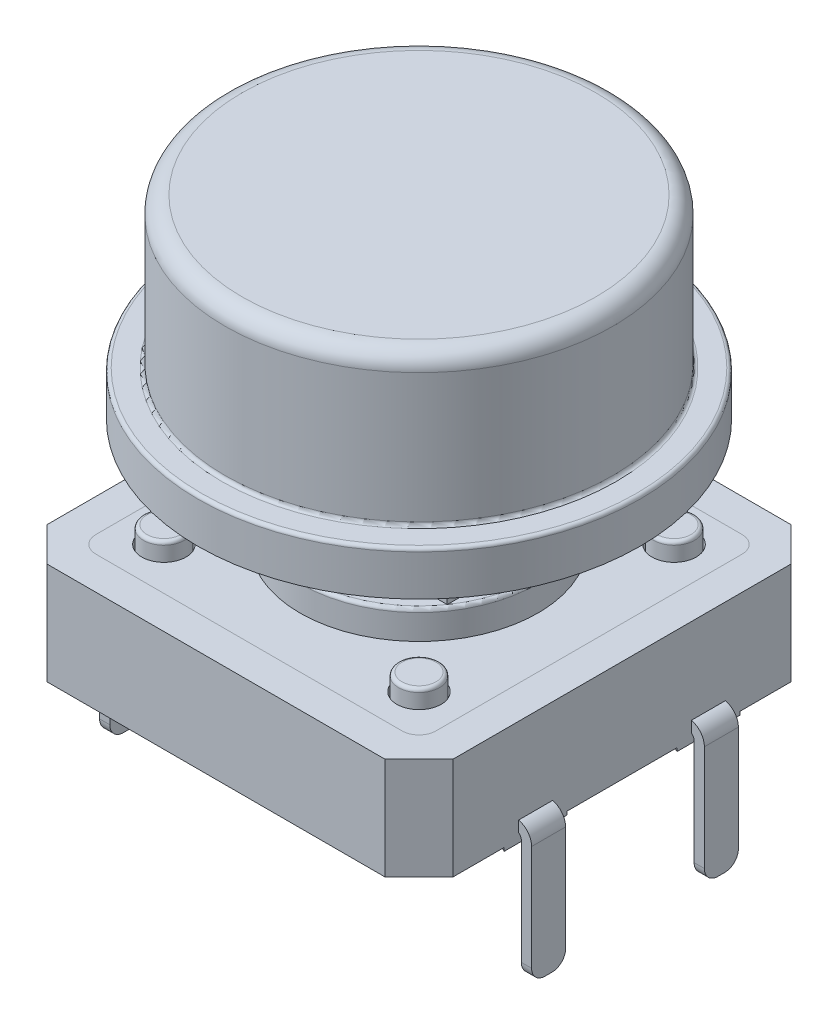
SolidWorks part; units mm, degrees
other "Metal Cover"
other "Button Body"
other "Plastic Button"
other "Connection 1"
other "Connection 2"
ref_plane "Front Plane" through (0, 0, 0) normal (0, 0, 1) x (1, 0, 0)
ref_plane "Top Plane" through (0, 0, 0) normal (0, 1, 0) x (1, 0, 0)
ref_plane "Right Plane" through (0, 0, 0) normal (1, 0, 0) x (0, 0, -1)
sketch "Sketch1" plane through (0, 0, 0) normal (0, 1, 0) x (1, 0, 0)
  line L0 (-5.97, 0) -> (5.97, 0) construction
  line L1 (-5.97, 5.97) -> (5.97, 5.97)
  line L2 (-5.97, 5.97) -> (-5.97, -5.97)
  line L3 (-5.97, -5.97) -> (5.97, -5.97)
  line L4 (5.97, 5.97) -> (5.97, -5.97)
  line L6 (-6.35, 2.54) -> (6.35, 2.54) construction
  line L7 (-6.35, 2.54) -> (-6.35, -2.54) construction
  line L8 (-6.35, -2.54) -> (6.35, -2.54) construction
  line L9 (6.35, 2.54) -> (6.35, -2.54) construction
  line L10 (-6.35, 2.54) -> (6.35, -2.54) construction
  line L11 (-6.35, -2.54) -> (6.35, 2.54) construction
  circle A0 centre (-6.35, 2.54) radius 1 construction
  circle A1 centre (6.35, 2.54) radius 1 construction
  circle A2 centre (6.35, -2.54) radius 1 construction
  circle A3 centre (-6.35, -2.54) radius 1 construction
  point P6 (0, 0)
  dimension "D5" = 2
  dimension "D1" = 11.94
  dimension "D2" = 11.94
  dimension "D3" = 12.7
  dimension "D4" = 5.08
extrude "Boss-Extrude1" add sketch "Sketch1" against normal blind 3
sketch "Sketch2" plane through (0, 0, 0) normal (0, 1, 0) x (1, 0, 0)
  line L1 (-5, 5) -> (5, 5)
  line L2 (-5, 5) -> (-5, -5)
  line L3 (-5, -5) -> (5, -5)
  line L4 (5, 5) -> (5, -5)
  line L5 (-5, 5) -> (5, -5) construction
  line L6 (-5, -5) -> (5, 5) construction
  point P0 (0, 0)
  dimension "D1" = 10
extrude "Cut-Extrude1" cut sketch "Sketch2" against normal blind 0.5
fillet "Fillet1" radius 0.5 4 edges at (-5, -0.25, 5) (5, -0.25, 5) (5, -0.25, -5) (-5, -0.25, -5)
chamfer "Chamfer1" distance 1 angle 45 4 edges at (5.97, -1.5, -5.97) (-5.97, -1.5, -5.97) (-5.97, -1.5, 5.97) (5.97, -1.5, 5.97)
sketch "Sketch3" plane through (0, -0.5, 0) normal (0, 1, 0) x (1, 0, 0)
  line L4 (-5, 4.5) -> (-5, -4.5)
  line L5 (-4.5, -5) -> (4.5, -5)
  line L6 (5, -4.5) -> (5, 4.5)
  line L7 (4.5, 5) -> (-4.5, 5)
  line L8 (-5, 4.5) -> (-5, -4.5)
  line L9 (-4.5, -5) -> (4.5, -5)
  line L10 (5, -4.5) -> (5, 4.5)
  line L11 (4.5, 5) -> (-4.5, 5)
  arc A4 (-5, -4.5) -> (-4.5, -5) centre (-4.5, -4.5) ccw
  arc A5 (4.5, -5) -> (5, -4.5) centre (4.5, -4.5) ccw
  arc A6 (5, 4.5) -> (4.5, 5) centre (4.5, 4.5) ccw
  arc A7 (-4.5, 5) -> (-5, 4.5) centre (-4.5, 4.5) ccw
  arc A8 (-5, -4.5) -> (-4.5, -5) centre (-4.5, -4.5) ccw
  arc A9 (4.5, -5) -> (5, -4.5) centre (4.5, -4.5) ccw
  arc A10 (5, 4.5) -> (4.5, 5) centre (4.5, 4.5) ccw
  arc A11 (-4.5, 5) -> (-5, 4.5) centre (-4.5, 4.5) ccw
  dimension "D1" = 0
extrude "Boss-Extrude2" add sketch "Sketch3" along normal blind 0.5 separate body
sketch "Sketch4" plane through (0, 0, 0) normal (0, 1, 0) x (1, 0, 0)
  line L1 (-3.75, 3.75) -> (3.75, 3.75) construction
  line L2 (-3.75, 3.75) -> (-3.75, -3.75) construction
  line L3 (-3.75, -3.75) -> (3.75, -3.75) construction
  line L4 (3.75, 3.75) -> (3.75, -3.75) construction
  line L5 (-3.75, 3.75) -> (3.75, -3.75) construction
  line L6 (-3.75, -3.75) -> (3.75, 3.75) construction
  circle A0 centre (0, 0) radius 3.5
  circle A1 centre (-3.75, 3.75) radius 0.65
  circle A2 centre (3.75, 3.75) radius 0.65
  circle A3 centre (3.75, -3.75) radius 0.65
  circle A4 centre (-3.75, -3.75) radius 0.65
  dimension "D1" = 7.5
  dimension "D2" = 7
  dimension "D3" = 1.3
extrude "Cut-Extrude2" cut sketch "Sketch4" against normal up to surface (0.5 mm away) up to face at (0, -0.5, 0)
sketch "Sketch5" plane through (0, -0.5, 0) normal (0, 1, 0) x (1, 0, 0)
  circle A0 centre (0, 0) radius 3.45 construction
  circle A1 centre (-3.75, 3.75) radius 0.6
  circle A2 centre (3.75, 3.75) radius 0.6
  circle A3 centre (3.75, -3.75) radius 0.6
  circle A4 centre (-3.75, -3.75) radius 0.6
  dimension "D1" = 6.9
  dimension "D2" = 1.2
extrude "Boss-Extrude3" add sketch "Sketch5" along normal blind 1
sketch "Sketch6" plane through (0, -0.5, 0) normal (0, 1, 0) x (1, 0, 0)
  circle A0 centre (0, 0) radius 3.45 construction
  circle A1 centre (0, 0) radius 3.45
extrude "Boss-Extrude4" add sketch "Sketch6" along normal blind 1.3
sketch "Sketch7" plane through (0, 0.8, 0) normal (0, 1, 0) x (1, 0, 0)
  line L1 (-1.35, 1.35) -> (1.35, 1.35)
  line L2 (-1.35, 1.35) -> (-1.35, -1.35)
  line L3 (-1.35, -1.35) -> (1.35, -1.35)
  line L4 (1.35, 1.35) -> (1.35, -1.35)
  line L5 (-1.35, 1.35) -> (1.35, -1.35) construction
  line L6 (-1.35, -1.35) -> (1.35, 1.35) construction
  point P0 (0, 0)
  dimension "D1" = 2.7
extrude "Boss-Extrude5" add sketch "Sketch7" along normal blind 1.3
sketch "Sketch8" plane through (0, 2.1, 0) normal (0, 1, 0) x (1, 0, 0)
  line L0 (0, 1.925) -> (0, -1.925) construction
  line L1 (-1.725, 1.925) -> (1.725, 1.925)
  line L2 (-1.925, 1.725) -> (-1.925, -1.725)
  line L3 (-1.725, -1.925) -> (1.725, -1.925)
  line L4 (1.925, 1.725) -> (1.925, -1.725)
  arc A0 (-1.725, 1.925) -> (-1.925, 1.725) centre (-1.725, 1.725) ccw
  arc A1 (-1.925, -1.725) -> (-1.725, -1.925) centre (-1.725, -1.725) ccw
  arc A2 (1.725, -1.925) -> (1.925, -1.725) centre (1.725, -1.725) ccw
  arc A3 (1.725, 1.925) -> (1.925, 1.725) centre (1.725, 1.725) cw
  dimension "D3" = 0.2
  dimension "D1" = 3.85
  dimension "D2" = 3.85
extrude "Boss-Extrude6" add sketch "Sketch8" along normal blind 2.1
sketch "Sketch9" plane through (0, 4.2, 0) normal (0, 1, 0) x (1, 0, 0)
  circle A0 centre (0, 0) radius 1
  dimension "D1" = 2
extrude "Cut-Extrude3" cut sketch "Sketch9" against normal blind 1.5
sketch "Sketch10" plane through (0, 0, 0) normal (1, 0, 0) x (0, 0, -1)
  line L0 (0, 0) -> (0, -3) construction
  line L1 (-4.97, -3) -> (4.97, -3) construction
  line L2 (0, 0) -> (0, 3.2) construction
  line L3 (0, 3.2) -> (-6.5, 3.2)
  line L4 (-6.5, 3.2) -> (-6.5, 4.4)
  line L5 (-6.4, 4.5) -> (-5.7, 4.5)
  line L6 (-5.7, 4.5) -> (-5.7, 8.4)
  line L7 (-5.2, 8.9) -> (0, 8.9)
  line L8 (0, 8.9) -> (0, 3.2)
  arc A0 (-5.7, 8.4) -> (-5.2, 8.9) centre (-5.2, 8.4) cw
  arc A1 (-6.5, 4.4) -> (-6.4, 4.5) centre (-6.4, 4.4) cw
  dimension "D1" = 6.5
  dimension "D6" = 0.5
  dimension "D7" = 0.1
  dimension "D2" = 5.7
  dimension "D3" = 1.3
  dimension "D4" = 3.2
  dimension "D5" = 5.7
revolve "Revolve1" add sketch "Sketch10" angle 360 about L8
sketch "Sketch11" plane through (0, 3.2, 0) normal (0, -1, 0) x (1, 0, 0)
  circle A0 centre (0, 0) radius 5
  dimension "D1" = 10
extrude "Cut-Extrude4" cut sketch "Sketch11" against normal blind 4
sketch "Sketch12" plane through (0, 7.2, 0) normal (0, -1, 0) x (1, 0, 0)
  line L0 (-1.55, 0) -> (1.55, 0) construction
  line L2 (1.55, 1.92) -> (2.75, 1.92)
  line L3 (1.55, 1.92) -> (1.55, -1.92)
  line L4 (1.55, -1.92) -> (2.75, -1.92)
  line L5 (2.75, 1.92) -> (2.75, -1.92)
  line L6 (-1.55, 1.92) -> (-2.75, 1.92)
  line L7 (-1.55, 1.92) -> (-1.55, -1.92)
  line L8 (-1.55, -1.92) -> (-2.75, -1.92)
  line L9 (-2.75, 1.92) -> (-2.75, -1.92)
  dimension "D1" = 5.5
  dimension "D2" = 3.84
  dimension "D3" = 1.2
extrude "Boss-Extrude7" add sketch "Sketch12" along normal offset from surface (6.4 mm away) 2.4 up to face at (0, 3.2, -5) offset beyond the face yes
sketch "Sketch13" plane through (0, 0, 1.92) normal (0, 0, 1) x (1, 0, 0)
  line L0 (-1.55, 0.8) -> (-1.55, 7.2) construction
  line L1 (-1.55, 2) -> (-2.05, 2)
  line L2 (-1.55, 2) -> (-1.55, 7.2)
  line L3 (-1.55, 7.2) -> (-2.05, 7.2)
  line L4 (-2.05, 2) -> (-2.05, 7.2)
  line L5 (-5, 7.2) -> (5, 7.2) construction
  line L6 (1.55, 0.8) -> (1.55, 7.2) construction
  line L7 (1.55, 2) -> (2.05, 2)
  line L8 (1.55, 2) -> (1.55, 7.2)
  line L9 (1.55, 7.2) -> (2.05, 7.2)
  line L10 (2.05, 2) -> (2.05, 7.2)
  line L11 (-2.75, 0.8) -> (-1.55, 0.8) construction
  line L12 (-2.75, 0.8) -> (-2.75, 7.2) construction
  dimension "D1" = 0.7
  dimension "D2" = 1.2
extrude "Cut-Extrude5" cut sketch "Sketch13" against normal up to surface (3.84 mm away) up to face at (-2.15, 4, -1.92)
fillet "Fillet2" radius 0.5 2 edges at (-1.55, 0.8, 0) (1.55, 0.8, 0)
fillet "Fillet3" radius 0.6 2 edges at (1.55, 2, 0) (-1.55, 2, 0)
fillet "Fillet4" radius 0.1 5 edges at (0, 0.8, 3.45) (-3.75, 0.5, 4.35) (3.75, 0.5, 4.35) (3.75, 0.5, -3.15) (-3.75, 0.5, -3.15)
sketch "Sketch14" plane through (0, 7.2, 0) normal (0, -1, 0) x (1, 0, 0)
  line L0 (0, 1.93) -> (0, -1.93) construction
  line L2 (-1, 2.75) -> (1, 2.75)
  line L3 (-1, 2.75) -> (-1, 1.93)
  line L4 (-1, 1.93) -> (1, 1.93)
  line L5 (1, 2.75) -> (1, 1.93)
  line L10 (-1, -1.93) -> (1, -1.93)
  line L11 (-1, -1.93) -> (-1, -2.75)
  line L12 (-1, -2.75) -> (1, -2.75)
  line L13 (1, -1.93) -> (1, -2.75)
  dimension "D1" = 2
  dimension "D2" = 0.82
  dimension "D3" = 5.5
extrude "Boss-Extrude8" add sketch "Sketch14" along normal blind 5.36
fillet "Fillet5" radius 0.1 1 edges at (0, 4.5, 5.7)
sketch "Sketch15" plane through (0, 7.2, 0) normal (0, -1, 0) x (1, 0, 0)
  line L0 (0, -2.75) -> (0, 2.75) construction
  line L1 (1, 2.75) -> (-1, 2.75) construction
  line L2 (2.75, 0) -> (-2.75, 0) construction
  line L3 (-0.3, 5.25) -> (0.3, 5.25)
  line L4 (-0.3, 5.25) -> (-0.3, 2.75)
  line L5 (-0.3, 2.75) -> (0.3, 2.75)
  line L6 (0.3, 5.25) -> (0.3, 2.75)
  line L7 (-0.3, -2.75) -> (0.3, -2.75)
  line L8 (-0.3, -2.75) -> (-0.3, -5.25)
  line L9 (-0.3, -5.25) -> (0.3, -5.25)
  line L10 (0.3, -2.75) -> (0.3, -5.25)
  line L11 (2.75, -1.92) -> (2.75, 1.92) construction
  line L13 (2.75, 0.3) -> (5.25, 0.3)
  line L14 (2.75, 0.3) -> (2.75, -0.3)
  line L15 (2.75, -0.3) -> (5.25, -0.3)
  line L16 (5.25, 0.3) -> (5.25, -0.3)
  line L17 (-2.75, 0.3) -> (-5.25, 0.3)
  line L18 (-2.75, 0.3) -> (-2.75, -0.3)
  line L19 (-2.75, -0.3) -> (-5.25, -0.3)
  line L20 (-5.25, 0.3) -> (-5.25, -0.3)
  dimension "D1" = 2.5
  dimension "D2" = 0.6
extrude "Boss-Extrude9" add sketch "Sketch15" along normal up to surface (4 mm away) up to face at (0, 3.2, -5)
ref_plane "Plane1" through (0, 0, 2.54) normal (0, 0, 1) x (1, 0, 0)
sketch "Sketch16" plane through (0, 0, 2.54) normal (0, 0, 1) x (1, 0, 0)
  line L0 (0, 0) -> (0, -2.5) construction
  line L1 (-4.97, 0) -> (4.97, 0) construction
  line L2 (-5.85, -2.5) -> (5.85, -2.5)
  line L3 (0, -2.5) -> (0, -3) construction
  line L4 (-4.97, -3) -> (4.97, -3) construction
  line L5 (6.35, -3) -> (6.35, -6.5)
  line L6 (6.35, -6.5) -> (6.05, -6.5)
  line L7 (6.05, -6.5) -> (6.05, -3)
  line L8 (5.85, -2.8) -> (-5.85, -2.8)
  line L9 (-6.05, -3) -> (-6.05, -6.5)
  line L10 (-6.05, -6.5) -> (-6.35, -6.5)
  line L11 (-6.35, -6.5) -> (-6.35, -3)
  arc A0 (-5.85, -2.8) -> (-6.05, -3) centre (-5.85, -3) ccw
  arc A1 (6.05, -3) -> (5.85, -2.8) centre (5.85, -3) ccw
  arc A2 (-5.85, -2.5) -> (-6.35, -3) centre (-5.85, -3) ccw
  arc A3 (5.85, -2.5) -> (6.35, -3) centre (5.85, -3) cw
  dimension "D5" = 0.2
  dimension "D6" = 0.5
  dimension "D1" = 0.5
  dimension "D2" = 0.3
  dimension "D3" = 0.3
  dimension "D4" = 4
  dimension "D7" = 12.7
extrude "Boss-Extrude10" add sketch "Sketch16" along normal mid plane 1 separate body
mirror "Mirror1" about plane through (0, 0, 0) normal (0, 0, 1) of bodies 116
sketch "Sketch18" plane through (0, -3, 0) normal (0, -1, 0) x (1, 0, 0)
  line L0 (-5.97, -4.97) -> (-5.97, 4.97) construction
  line L1 (-5.97, -3.465) -> (-5.97, -1.615)
  line L2 (5.97, 4.97) -> (5.97, -4.97) construction
  line L3 (5.97, 3.465) -> (5.97, 1.615)
  line L4 (5.97, -1.615) -> (5.97, -3.465)
  line L5 (-5.97, 1.615) -> (-5.97, 3.465)
  line L6 (-5, 0) -> (5, 0) construction
  line L7 (-3, 5) -> (3, 5)
  line L8 (-5, 3) -> (-5, -3)
  line L9 (-3, -5) -> (3, -5)
  line L10 (5, 3) -> (5, -3)
  circle A0 centre (-6.35, 2.54) radius 1 construction
  arc A1 (-5.97, 1.615) -> (-5.97, 3.465) centre (-6.35, 2.54) ccw
  circle A2 centre (6.35, 2.54) radius 1 construction
  arc A3 (5.97, 3.465) -> (5.97, 1.615) centre (6.35, 2.54) ccw
  circle A4 centre (-6.35, -2.54) radius 1 construction
  arc A5 (-5.97, -3.465) -> (-5.97, -1.615) centre (-6.35, -2.54) ccw
  circle A6 centre (6.35, -2.54) radius 1 construction
  arc A7 (5.97, -1.615) -> (5.97, -3.465) centre (6.35, -2.54) ccw
  arc A8 (-3, 5) -> (-5, 3) centre (-3, 3) ccw
  arc A9 (-5, -3) -> (-3, -5) centre (-3, -3) ccw
  arc A10 (3, -5) -> (5, -3) centre (3, -3) ccw
  arc A11 (3, 5) -> (5, 3) centre (3, 3) cw
  dimension "D3" = 2
  dimension "D1" = 10
  dimension "D2" = 10
extrude "Boss-Extrude12" add sketch "Sketch18" along normal blind 0.1
sketch "Sketch19" plane through (0, -3.1, 0) normal (0, -1, 0) x (1, 0, 0)
  line L0 (-3, 5) -> (-3, 3)
  line L1 (-3, 3) -> (-5, 3)
  line L2 (3, 5) -> (3, 3)
  line L3 (3, 3) -> (5, 3)
  line L4 (-5, 3) -> (-5, -3)
  line L5 (-3, -5) -> (3, -5)
  line L6 (5, -3) -> (5, 3)
  line L7 (3, 5) -> (-3, 5)
  line L8 (-5, 3) -> (-5, -3)
  line L9 (-3, -5) -> (3, -5)
  line L10 (5, -3) -> (5, 3)
  line L11 (3, 5) -> (-3, 5)
  line L12 (-5, -3) -> (-3, -3)
  line L13 (-3, -3) -> (-3, -5)
  line L14 (3, -5) -> (3, -3)
  line L15 (3, -3) -> (5, -3)
  line L17 (-3, 3) -> (3, 3) construction
  line L18 (-3, 3) -> (-3, -3) construction
  line L19 (-3, -3) -> (3, -3) construction
  line L20 (3, 3) -> (3, -3) construction
  line L21 (-3, 3) -> (3, -3) construction
  line L22 (-3, -3) -> (3, 3) construction
  arc A4 (-3, 5) -> (-5, 3) centre (-3, 3) ccw
  arc A5 (-5, -3) -> (-3, -5) centre (-3, -3) ccw
  arc A6 (3, -5) -> (5, -3) centre (3, -3) ccw
  arc A7 (5, 3) -> (3, 5) centre (3, 3) ccw
  point P0 (0, 0)
  dimension "D1" = 0
extrude "Cut-Extrude6" cut sketch "Sketch19" against normal up to surface (0.1 mm away) up to face at (0, -3, 0)
fillet "Fillet6" radius 0.4 4 edges at (-6.2, -6.5, 3.04) (-6.2, -6.5, 2.04) (6.2, -6.5, 2.04) (6.2, -6.5, 3.04)
fillet "Fillet7" radius 0.4 4 edges at (-6.2, -6.5, -3.04) (-6.2, -6.5, -2.04) (6.2, -6.5, -2.04) (6.2, -6.5, -3.04)
